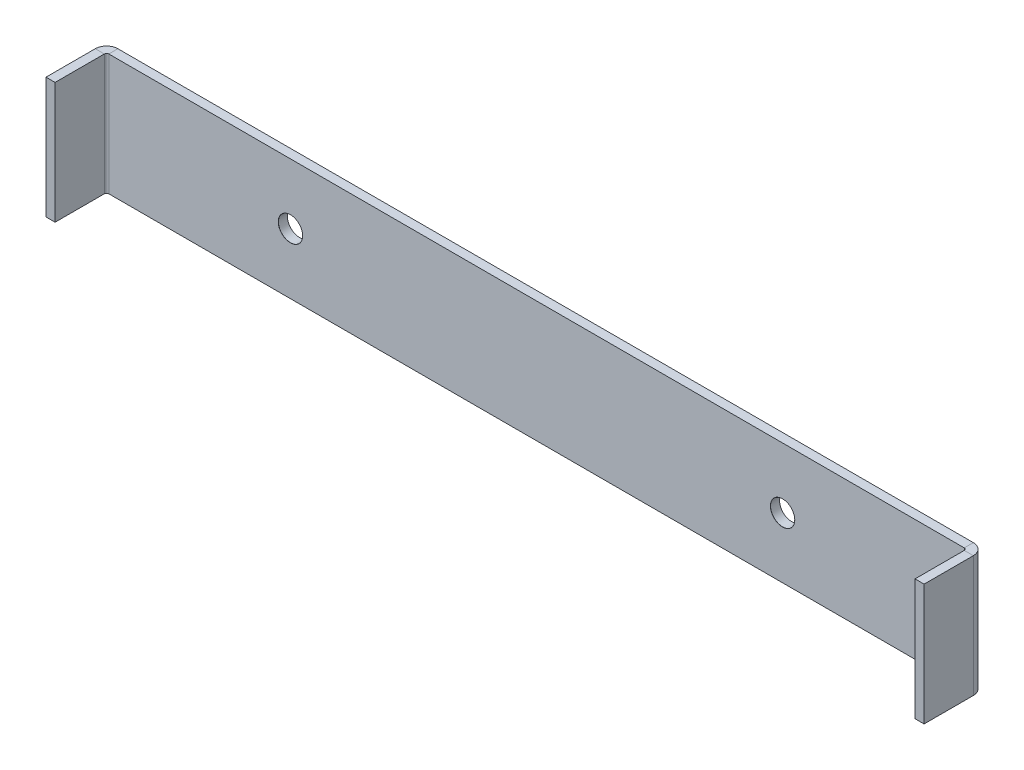
SolidWorks part; units mm, degrees
note: The reader was unsure of these and kept them because the rebuilt part matched: flange length of "Edge-Flange1", "Edge-Flange2".
ref_plane "Front Plane" through (0, 0, 0) normal (0, 0, 1) x (1, 0, 0)
ref_plane "Top Plane" through (0, 0, 0) normal (0, 1, 0) x (1, 0, 0)
ref_plane "Right Plane" through (0, 0, 0) normal (1, 0, 0) x (0, 0, -1)
sketch "Sketch1" plane through (0, 0, 0) normal (0, 0, 1) x (1, 0, 0)
  line L1 (0, 0) -> (290, 0)
  line L2 (0, 0) -> (0, 40)
  line L3 (0, 40) -> (290, 40)
  line L4 (290, 0) -> (290, 40)
  dimension "D1" = 40
  dimension "D2" = 290
base flange "Base-Flange1" sketch "Sketch1" thickness 3 reverse thickness direction no parameters "D1"=0.7366
edge flange "Edge-Flange1" sketch "Sketch8" flange angle 90 flange length 20 flange position material inside bend radius 0.7366 thickness 3 relief rectangular parameters "D6"=10
sketch "Sketch8" plane through (0, 0, 0) normal (-1, 0, 0) x (0, -1, 0)
  line L0 (-40, 0) -> (0, 0) construction
  line L1 (-40, 0) -> (0, 0)
  line L2 (-40, 0) -> (-40, 17)
  line L3 (-40, 17) -> (0, 17)
  line L4 (0, 17) -> (0, 0)
bend "EdgeBend1" bend radius 0.7366 bend angle 90 parameters "D5"=1
edge flange "Edge-Flange2" sketch "Sketch11" flange angle 90 flange length 20 flange position material inside bend radius 0.7366 thickness 3 relief rectangular parameters "D6"=10
sketch "Sketch11" plane through (290, 0, 0) normal (1, 0, 0) x (0, 1, 0)
  line L0 (0, 0) -> (40, 0) construction
  line L1 (0, 0) -> (40, 0)
  line L2 (0, 0) -> (0, 17)
  line L3 (0, 17) -> (40, 17)
  line L4 (40, 17) -> (40, 0)
bend "EdgeBend2" bend radius 0.7366 bend angle 90 parameters "D5"=2
hole_wizard "Ø8.0mm Dowel Hole1" positions "Sketch15" profile "Sketch13" hole size "Ø8.0" standard "ANSI Metric" end condition through all
sketch "Sketch15" plane through (0, 0, 0) normal (0, 0, 1) x (1, 0, 0)
  line L1 (286.2634, 40) -> (286.2634, 0) construction
  line L2 (3.7366, 0) -> (286.2634, 0) construction
  line L3 (3.7366, 0) -> (3.7366, 40) construction
  point P8 (226.2634, 20)
  point P18 (63.7366, 20)
  dimension "D1" = 20
  dimension "D2" = 60
  dimension "D3" = 60
  dimension "D4" = 20
sketch "Sketch13" plane through (226.2634, 20, 0) normal (1, 0, 0) x (0, -1, 0)
  line L0 (0, 0) -> (0, 3)
  line L1 (0, 3) -> (4, 3)
  line L2 (4, 3) -> (4, 0.025)
  line L3 (4, 0.025) -> (4.025, 0)
  line L5 (4.025, 0) -> (0, 0)
  line L6 (-4, 0.025) -> (-4.025, 0) construction
  line L11 (0, -6.35) -> (0, 107.95) construction
  dimension "Thru Hole Dia." = 8
  dimension "Thru Hole Depth" = 3
  dimension "Near C'Sink Dia." = 8.05
  dimension "Near C'Sink Angle" = 90
sketch "Bend-Lines1" [suppressed] plane through (0, 0, 0) normal (0, 1, 0) x (1, 0, 0)
sketch "Bounding-Box1" [suppressed] plane through (0, 0, 0) normal (0, 1, 0) x (1, 0, 0)
sheet metal parameters "Sheet-Metal1" thickness 3 parameters "D1"=0.7366
flat pattern "Flat-Pattern1" [suppressed]
sketch "Bend-Lines2" plane through (0, 0, 0) normal (0, 1, 0) x (1, 0, 0)
sketch3d "Bounding-Box2" [suppressed]
  line L0 (0, 0, 0) -> (-290, 0, 0) construction
  line L1 (0, 40, 0) -> (-290, 40, 0) construction
  line L2 (0, 0, 0) -> (0, 40, 0) construction
  line L3 (-290, 0, 0) -> (-290, 40, 0) construction
sheet metal parameters "Sheet-Metal2" thickness 3 parameters "D1"=0.7366
flat pattern "Flat-Pattern1"
sketch "Bend-Lines2" plane through (0, 0, 0) normal (0, 0, 1) x (1, 0, 0)
  line L0 (1.98, 40) -> (1.98, 0) construction
  line L1 (1.98, 40) -> (1.98, 0) construction
sketch3d "Bounding-Box2" [suppressed]
  line L0 (-16.04, 0, 0) -> (290, 0, 0) construction
  line L1 (-16.04, 40, 0) -> (290, 40, 0) construction
  line L2 (-16.04, 0, 0) -> (-16.04, 40, 0) construction
  line L3 (290, 0, 0) -> (290, 40, 0) construction
bend of the flat pattern "Flatten-<EdgeBend1>1"
sheet metal parameters "Sheet-Metal3" thickness 3 parameters "D1"=0.7366
flat pattern "Flat-Pattern1"
sketch "Bend-Lines2" plane through (0, 0, 0) normal (0, 0, 1) x (1, 0, 0)
  line L0 (1.98, 40) -> (1.98, 0) construction
  line L1 (1.98, 40) -> (1.98, 0) construction
  line L2 (288.02, 0) -> (288.02, 40) construction
  line L3 (288.02, 0) -> (288.02, 40) construction
sketch3d "Bounding-Box2" [suppressed]
  line L0 (-16.04, 0, 0) -> (306.04, 0, 0) construction
  line L1 (-16.04, 40, 0) -> (306.04, 40, 0) construction
  line L2 (-16.04, 0, 0) -> (-16.04, 40, 0) construction
  line L3 (306.04, 0, 0) -> (306.04, 40, 0) construction
bend of the flat pattern "Flatten-<EdgeBend1>1"
bend of the flat pattern "Flatten-<EdgeBend2>1"
sheet metal parameters "Sheet-Metal4" thickness 3 parameters "D1"=0.7366
flat pattern "Flat-Pattern1"
sketch "Bend-Lines2" plane through (0, 0, 0) normal (0, 0, 1) x (1, 0, 0)
  line L0 (1.98, 40) -> (1.98, 0) construction
  line L1 (1.98, 40) -> (1.98, 0) construction
  line L2 (288.02, 0) -> (288.02, 40) construction
  line L3 (288.02, 0) -> (288.02, 40) construction
sketch3d "Bounding-Box2" [suppressed]
  line L0 (-16.04, 0, 0) -> (306.04, 0, 0) construction
  line L1 (-16.04, 40, 0) -> (306.04, 40, 0) construction
  line L2 (-16.04, 0, 0) -> (-16.04, 40, 0) construction
  line L3 (306.04, 0, 0) -> (306.04, 40, 0) construction
bend of the flat pattern "Flatten-<EdgeBend1>1"
bend of the flat pattern "Flatten-<EdgeBend2>1"
